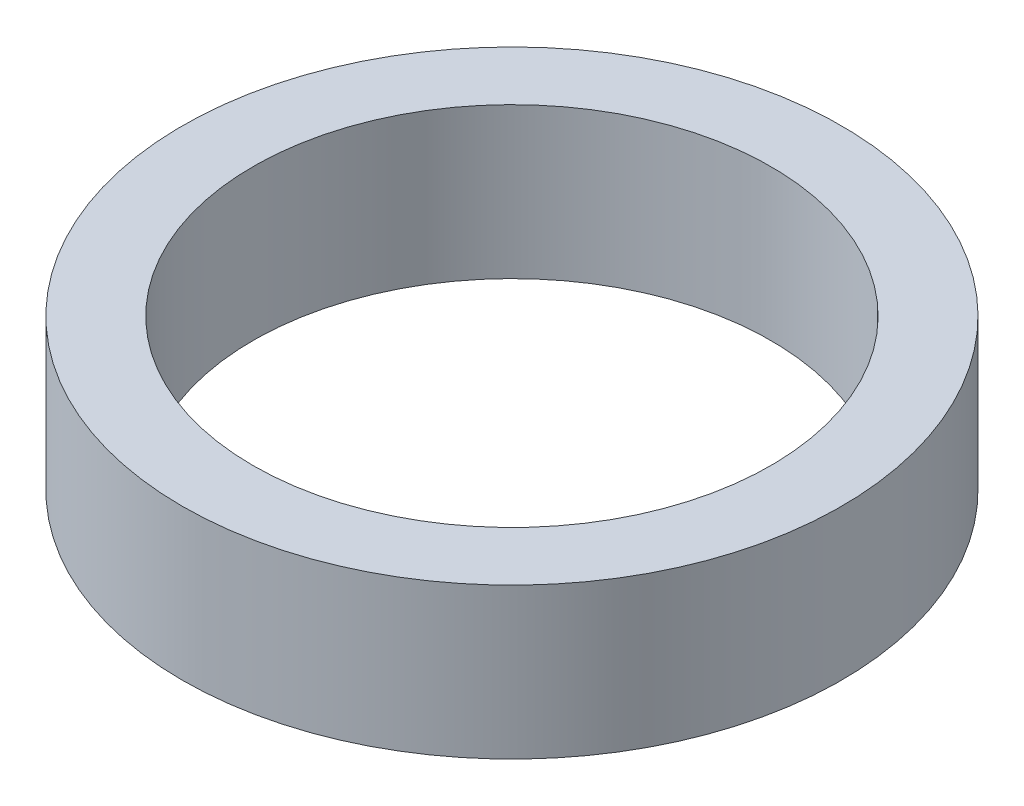
SolidWorks part; units mm, degrees
ref_plane "Front Plane" through (0, 0, 0) normal (0, 0, 1) x (1, 0, 0)
ref_plane "Top Plane" through (0, 0, 0) normal (0, 1, 0) x (1, 0, 0)
ref_plane "Right Plane" through (0, 0, 0) normal (1, 0, 0) x (0, 0, -1)
sketch "Sketch1" plane through (0, 0, 0) normal (0, 1, 0) x (1, 0, 0)
  circle A0 centre (0, 0) radius 35
  dimension "FLANGE_OD" = 70
extrude "Boss-Extrude1" add sketch "Sketch1" along normal blind 16
sketch "Sketch2" plane through (0, 0, 0) normal (0, 1, 0) x (1, 0, 0)
  circle A0 centre (0, 0) radius 27.5
  dimension "BORE_D" = 55
extrude "Cut-Extrude1" cut sketch "Sketch2" along normal through all
sketch "Sketch3" plane through (0, 16, 0) normal (0, 1, 0) x (1, 0, 0)
  circle A0 centre (0, 0) radius 15.5124 construction
  circle A1 centre (-15.5124, 0) radius 1.5
  dimension "BOLT_D" = 3
  dimension "BOLT_PCD" = 31.0248
extrude "Cut-Extrude2" cut sketch "Sketch3" against normal blind 10.8021 rebuild error yes
pattern_circular "CirPattern1" count 6 over 360 rebuild error yes
